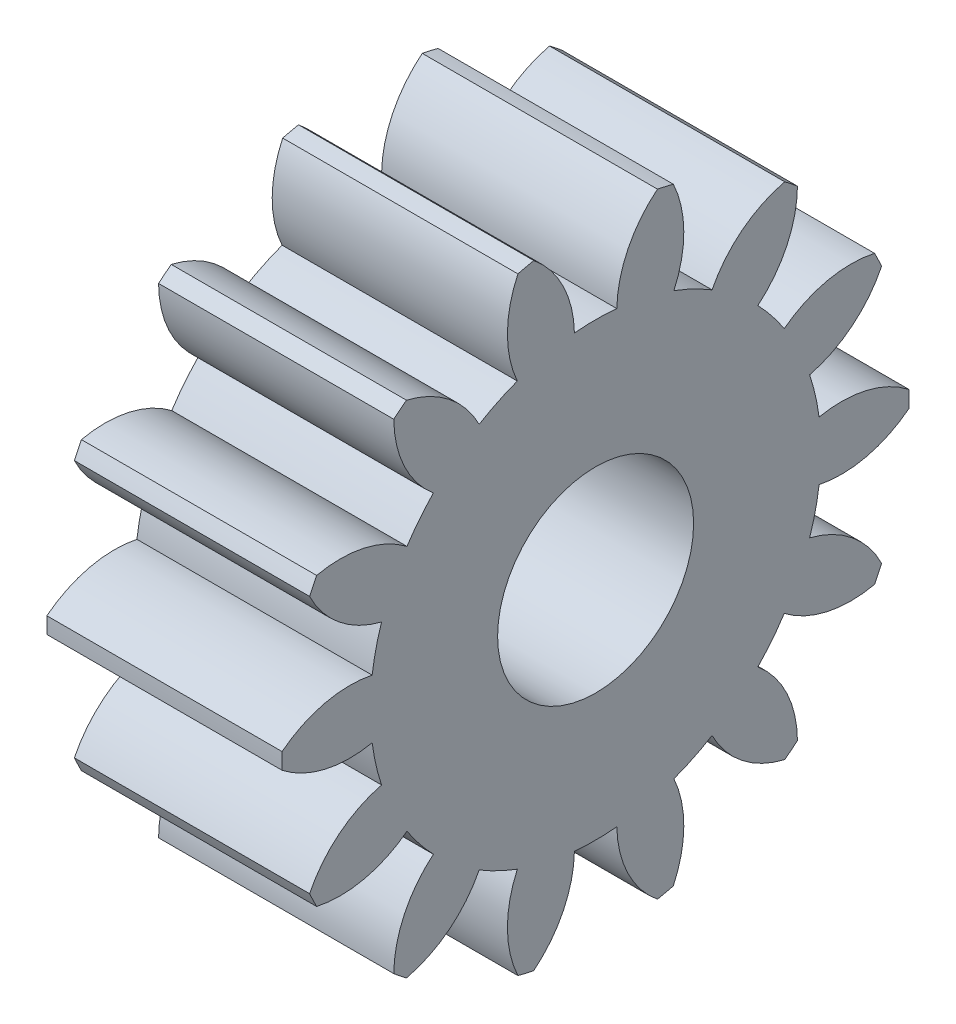
SolidWorks part; units mm, degrees
ref_plane "Plane1" through (0, 0, 0) normal (0, 0, 1) x (1, 0, 0)
ref_plane "Plane2" through (0, 0, 0) normal (0, 1, 0) x (1, 0, 0)
ref_plane "Plane3" through (0, 0, 0) normal (1, 0, 0) x (0, 0, -1)
other "Configuration Table"
sketch "HoldingSke" plane through (0, 0, 0) normal (0, 1, 0) x (1, 0, 0)
  line L0 (0, 0) -> (0.9703, -0.2419)
  line L1 (-15, 0) -> (100, 0) construction
  line L2 (0, 0) -> (-2.1039, 2.3779)
  line L3 (0, 0) -> (-11.863, 4.5341)
  line L4 (0, 0) -> (8.3795, 2.0892)
  line L5 (0, 0) -> (-9.3695, -3.4946)
  line L6 (0, 0) -> (-4.9738, -3.3558)
  line L7 (-2.1039, 2.3779) -> (0.0486, 12.1435)
  line L8 (-76.2, 54.61) -> (-75.3, 54.61)
  line L9 (-71.009, 38.7566) -> (-53.1078, 45.2721)
  line L10 (-76.2, 71.12) -> (104.1128, 71.12)
  line L11 (0, 0) -> (-6, 0)
  line L12 (-76.2, 101.6) -> (-76.162, 101.6)
  line L13 (24.9733, 27.94) -> (52.9518, 28.4284)
  line L14 (24.9733, 27.94) -> (24.9743, 27.94)
  line L15 (24.9733, 27.94) -> (100.4006, 29.5858)
  line L16 (-63.627, -1) -> (-12.827, -1)
  circle A0 centre (0, 0) radius 2.5
  circle A1 centre (0, 0) radius 5.749
  circle A2 centre (0, 0) radius 37.5
  circle A3 centre (0, 0) radius 2.5
  dimension "Num_teeth" = 14
  dimension "Pitch_radius" = 180.3128
  dimension "Width" = 6
  dimension "Thickness" = 6
sketch "BasProSke" plane through (0, 0, 0) normal (0, 1, 0) x (1, 0, 0)
  line L0 (-10, 0) -> (60, 0) construction
  line L1 (0, 0) -> (0, 8)
  line L2 (0, 0) -> (6, 0)
  line L3 (6, 0) -> (6, 8)
  line L4 (6, 8) -> (0, 8)
  dimension "Thickness" = 6
  dimension "Diameter" = 16
revolve "Base-Revolve" add sketch "BasProSke" angle 360 about L0
sketch "TooCutSke" plane through (0, 0, 0) normal (1, 0, 0) x (0, 0, -1)
  line L1 (0, 0) -> (0, 107) construction
  line L2 (0, 0) -> (-0.8502, 6.9482) construction
  line L3 (0, 0) -> (-3.0989, 13.5772) construction
  line L4 (-0.8502, 6.9482) -> (-1.5494, 6.7886) construction
  arc A0 (0.5404, 5.7235) -> (-0.5404, 5.7235) centre (0, 0) ccw
  arc A1 (1.6036, 7.8636) -> (-1.6036, 7.8636) centre (0, 0) ccw
  circle A2 centre (0, 0) radius 7 construction
  circle A3 centre (0, 0) radius 6.5778 construction
  arc A4 (-0.5404, 5.7235) -> (-1.6036, 7.8636) centre (-3.3398, 5.6669) ccw
  arc A5 (1.6036, 7.8636) -> (0.5404, 5.7235) centre (3.3398, 5.6669) ccw
extrude "ToothCut" cut sketch "TooCutSke" along normal through all
fillet "Breaks" [suppressed] radius 0.02 tangent propagation no
fillet "RootFillets" [suppressed] radius 0.251
pattern_circular "TeethCuts" count 14 every 25.714 about axis through (-10, 0, 0) along (1, 0, 0) of "ToothCut", "RootFillets", "Breaks"
sketch "HubNeaOneSke" plane through (0, 0, 0) normal (-1, 0, 0) x (0, 0, 1)
  circle A0 centre (0, 0) radius 5.749
  dimension "Diameter" = 11.498
extrude "HubNearOne" [suppressed] add sketch "HubNeaOneSke" along normal blind 4.0001
sketch "HubNeaBotSke" plane through (0, 0, 0) normal (-1, 0, 0) x (0, 0, 1)
  circle A0 centre (0, 0) radius 5.749
  dimension "Diameter" = 11.498
extrude "HubNearBoth" [suppressed] add sketch "HubNeaBotSke" along normal blind 2
ref_plane "FarPln" through (6, 0, 0) normal (1, 0, 0) x (0, 0, -1)
sketch "HubFarSke" plane through (6, 0, 0) normal (1, 0, 0) x (0, 0, -1)
  circle A0 centre (0, 0) radius 5.749
  dimension "Diameter" = 11.498
extrude "HubFar" [suppressed] add sketch "HubFarSke" along normal blind 2
sketch "BorSke" plane through (0, 0, 0) normal (1, 0, 0) x (0, 0, -1)
  circle A0 centre (0, 0) radius 2.5
  dimension "Diameter" = 5
extrude "Bore" cut sketch "BorSke" along normal mid plane 20.0001
sketch "KeySke" plane through (0, 0, 0) normal (1, 0, 0) x (0, 0, -1)
  line L0 (-1, 0) -> (-1, 3.4)
  line L1 (-1, 3.4) -> (1, 3.4)
  line L2 (1, 3.4) -> (1, 0)
  line L3 (0, 0) -> (0, 34) construction
  line L4 (-1, 0) -> (1, 0)
  dimension "Width" = 2
extrude "Keyway" [suppressed] cut sketch "KeySke" along normal mid plane 20.0001
pattern_circular "Keyway2" [suppressed] count 2 every 90 about axis through (-10, 0, 0) along (1, 0, 0) reverse direction yes
equation "' \"Module@HoldingSke\" = 6.35"
equation "' \"Num_teeth@HoldingSke\" = 12"
equation "' \"Ap@HoldingSke\" =  20"
equation "' \"Ap@HoldingSke\" = 20"
equation "' \"Width@HoldingSke\" = 0.5 * 25.4"
equation "' \"Hub_dia@HoldingSke\"= 1 * 25.4"
equation "' \"Hub_dia@HoldingSke\" = 1 * 25.4"
equation "' \"Overall_len@HoldingSke\" = 1.0 * 25.4"
equation "' \"Bore@HoldingSke\" = 0.75 * 25.4"
equation "' \"T_dim@HoldingSke\" = 0.1 * 25.4"
equation "' \"Width@KeySke\" = 0.25 * 25.4"
equation "' \"Show_teeth@HoldingSke\" = 13"
equation "' \"Backlash@HoldingSke\" = 0.009 * 25.4"
equation "' \"Addendum_fac@HoldingSke\" = 1.0"
equation "' \"Dedendum_fac@HoldingSke\" = 1.25"
equation "' \"Dedendum_add@HoldingSke\" = 0.00005 * 25.4"
equation "' \"Clearance_fac@HoldingSke\" = 0.25"
equation "\"Pitch@HoldingSke\" = 1 / \"Module@HoldingSke\""
equation "\"Overcut_dia@TooCutSke\" = (\"Num_teeth@HoldingSke\" + 2 * \"Addendum_fac@HoldingSke\") / \"Pitch@HoldingSke\" + 0.002 * 25.4"
equation "\"Pitch_dia@TooCutSke\" = \"Num_teeth@HoldingSke\" / \"Pitch@HoldingSke\""
equation "\"Base_dia@TooCutSke\" = \"Num_teeth@HoldingSke\" / \"Pitch@HoldingSke\" * cos((\"Ap@HoldingSke\"  * 3.14159265 / 180))"
equation "\"Root_dia@TooCutSke\" = (\"Num_teeth@HoldingSke\" + 2) / \"Pitch@HoldingSke\" - 2 * (\"Addendum_fac@HoldingSke\" + \"Dedendum_fac@HoldingSke\") / \"Pitch@HoldingSke\" - \"Dedendum_add@HoldingSke\" * 2"
equation "\"Half_ang@TooCutSke\" = 180 / \"Num_teeth@HoldingSke\""
equation "\"Half_CT@TooCutSke\" = \"Num_teeth@HoldingSke\" / \"Pitch@HoldingSke\" * sin((3.14159265 / 2 / \"Num_teeth@HoldingSke\")) / 2 - 7 * \"Backlash@HoldingSke\" / 4"
equation "\"Flank_rad@TooCutSke\" = \"Num_teeth@HoldingSke\" / \"Pitch@HoldingSke\" / 5"
equation "\"Radius@RootFillets\" = \"Clearance_fac@HoldingSke\" / \"Pitch@HoldingSke\" + \"Dedendum_add@HoldingSke\""
equation "\"Break_rad@Breaks\" = 0.02 / \"Pitch@HoldingSke\""
equation "\"Thickness@HoldingSke\" = \"Width@HoldingSke\""
equation "\"OAL@HoldingSke\" = \"Thickness@HoldingSke\""
equation "\"MHD@HoldingSke\" = (\"Num_teeth@HoldingSke\" + 2) / \"Pitch@HoldingSke\" - 2 * (\"Addendum_fac@HoldingSke\" + \"Dedendum_fac@HoldingSke\")  / \"Pitch@HoldingSke\" - \"Dedendum_add@HoldingSke\" * 2"
equation "\"MBD@HoldingSke\" = (\"Num_teeth@HoldingSke\" + 2) / \"Pitch@HoldingSke\" - 2 * (\"Addendum_fac@HoldingSke\" + \"Dedendum_fac@HoldingSke\")  / \"Pitch@HoldingSke\" - \"Dedendum_add@HoldingSke\" * 2 - 0.002 * 25.4"
equation "\"MHD@HoldingSke\" = ((sgn( \"MHD@HoldingSke\" - \"Hub_dia@HoldingSke\" )-1)*( \"MHD@HoldingSke\" - \"Hub_dia@HoldingSke\" ))/-2+ \"Hub_dia@HoldingSke\""
equation "\"MBD@HoldingSke\" = ((sgn( \"MBD@HoldingSke\" - \"Bore@HoldingSke\" )-1)*( \"MBD@HoldingSke\" - \"Bore@HoldingSke\" ))/-2+ \"Bore@HoldingSke\""
equation "\"OAL@HoldingSke\" = ((sgn( \"OAL@HoldingSke\" - \"Overall_len@HoldingSke\" )+1)*( \"OAL@HoldingSke\" - \"Overall_len@HoldingSke\" ))/2 + \"Overall_len@HoldingSke\" + 0.000002 * 25.4"
equation "\"Num_teeth@TeethCuts\" = int( \"Show_teeth@HoldingSke\" ) + 1"
equation "\"Num_teeth@TeethCuts\" = ((sgn( \"Num_teeth@TeethCuts\" - \"Num_teeth@HoldingSke\" )-1)*( \"Num_teeth@TeethCuts\" - \"Num_teeth@HoldingSke\" ))/-2+ \"Num_teeth@HoldingSke\""
equation "\"Num_teeth@TeethCuts\" = ((sgn( \"Num_teeth@TeethCuts\" - 2.0)+1)*( \"Num_teeth@TeethCuts\" - 2.0))/2 +2.0"
equation "\"Angle@TeethCuts\" = 360.0 / \"Num_teeth@HoldingSke\""
equation "\"Diameter@BasProSke\" = (\"Num_teeth@HoldingSke\" + 2 * \"Addendum_fac@HoldingSke\") / \"Pitch@HoldingSke\""
equation "\"Thickness@BasProSke\"  = \"Thickness@HoldingSke\""
equation "' \"Fillet_rad@BasProSke\" =  \"Thickness@HoldingSke\" * 0.05"
equation "' \"Fillet_rad@BasProSke\" = \"Thickness@HoldingSke\" * 0.05"
equation "\"MHD@HoldingSke\" = ((sgn( \"MHD@HoldingSke\" - \"Root_dia@TooCutSke\" )-1)*( \"MHD@HoldingSke\" - \"Root_dia@TooCutSke\" ))/-2+ \"Root_dia@TooCutSke\""
equation "\"Diameter@HubNeaOneSke\" = \"MHD@HoldingSke\""
equation "\"Length@HubNearOne\" = \"OAL@HoldingSke\" - \"Thickness@BasProSke\""
equation "\"Diameter@HubNeaBotSke\" = \"MHD@HoldingSke\""
equation "\"Length@HubNearBoth\" = ( \"OAL@HoldingSke\" - \"Thickness@BasProSke\" ) / 2.0"
equation "\"Thickness@FarPln\" = \"Thickness@BasProSke\""
equation "\"Diameter@HubFarSke\" = \"MHD@HoldingSke\""
equation "\"Length@HubFar\" = ( \"OAL@HoldingSke\" - \"Thickness@BasProSke\" ) / 2.0"
equation "\"Diameter@BorSke\" = \"MBD@HoldingSke\""
equation "\"D1@Bore\" = \"OAL@HoldingSke\" * 2.0"
equation "\"D1@Keyway\" = \"OAL@HoldingSke\" * 2.0"
equation "\"Offset@KeySke\" = \"T_dim@HoldingSke\" + \"MBD@HoldingSke\" / 2.0"
